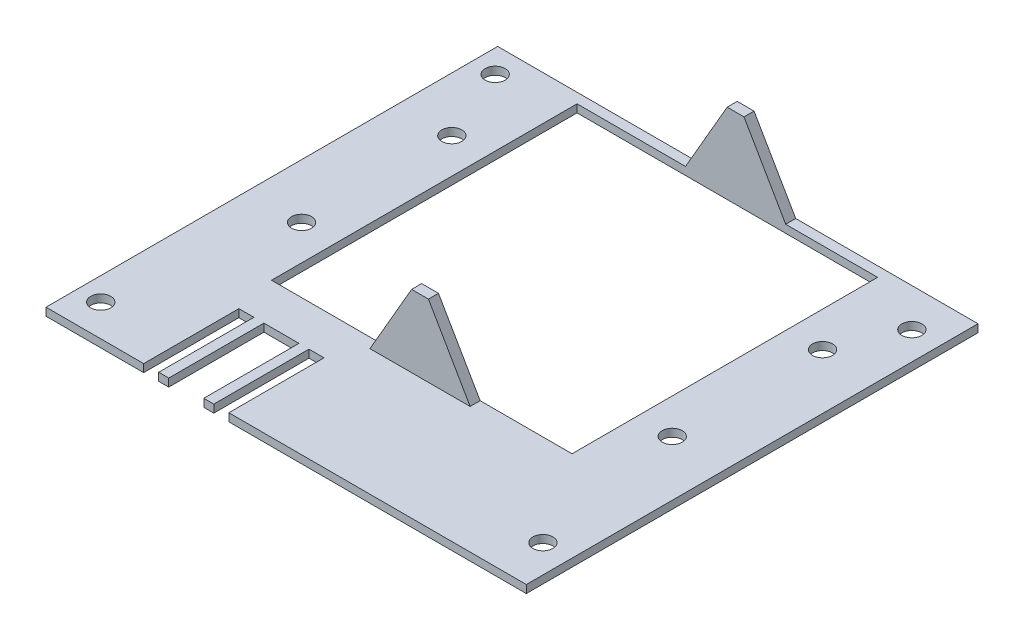
SolidWorks part; units mm, degrees
material "ABS"
ref_plane "Front Plane" through (0, 0, 0) normal (0, 0, 1) x (1, 0, 0)
ref_plane "Top Plane" through (0, 0, 0) normal (0, 1, 0) x (1, 0, 0)
ref_plane "Right Plane" through (0, 0, 0) normal (1, 0, 0) x (0, 0, -1)
sketch "Sketch1" plane through (0, 0, 0) normal (0, 1, 0) x (1, 0, 0)
  line L1 (-32.2441, 108.719) -> (64.6459, 108.719)
  line L2 (-32.2441, 108.719) -> (-32.2441, 18.549)
  line L3 (-32.2441, 18.549) -> (64.6459, 18.549)
  line L4 (64.6459, 108.719) -> (64.6459, 18.549)
  dimension "D1" = 96.89
  dimension "D2" = 90.17
extrude "PCB" add sketch "Sketch1" along normal blind 1.57
sketch "Sketch2" plane through (0, 1.57, 0) normal (0, 1, 0) x (1, 0, 0)
  line L1 (-32.2441, 18.549) -> (64.6459, 18.549) construction
  line L2 (-32.2441, 108.719) -> (-32.2441, 18.549) construction
  line L3 (-32.2441, 18.549) -> (64.6459, 18.549) construction
  circle A0 centre (58.5659, 27.439) radius 2
  circle A1 centre (-27.1641, 24.899) radius 2
  circle A2 centre (-27.1641, 103.639) radius 2
  circle A3 centre (58.5659, 101.099) radius 2
  dimension "D3" = 4
  dimension "D6" = 4
  dimension "D11" = 4
  dimension "D12" = 4
  dimension "D2" = 90.81
  dimension "D4" = 90.81
  dimension "D5" = 6.35
  dimension "D7" = 5.08
  dimension "D8" = 5.08
  dimension "D9" = 82.55
  dimension "D10" = 85.09
  dimension "D13" = 8.89
extrude "M3 Mounting Holes" cut sketch "Sketch2" against normal blind 1.57
sketch "Sketch3" plane through (0, 1.57, 0) normal (0, 1, 0) x (1, 0, 0)
  line L0 (64.6459, 108.719) -> (-32.2441, 108.719) construction
  line L1 (12.7559, 108.719) -> (22.7559, 108.719)
  line L2 (12.7559, 108.719) -> (12.7559, 106.719)
  line L3 (12.7559, 106.719) -> (22.7559, 106.719)
  line L4 (22.7559, 108.719) -> (22.7559, 106.719)
  line L5 (-32.2441, 108.719) -> (-32.2441, 18.549) construction
  line L7 (12.7559, 45.719) -> (22.7559, 45.719)
  line L8 (12.7559, 45.719) -> (12.7559, 43.719)
  line L9 (12.7559, 43.719) -> (22.7559, 43.719)
  line L10 (22.7559, 45.719) -> (22.7559, 43.719)
  dimension "D1" = 2
  dimension "D2" = 10
  dimension "D3" = 0
  dimension "D4" = 45
  dimension "D5" = 61
  dimension "D6" = 2
  dimension "D7" = 45
extrude "Boss-Extrude1" [suppressed] add sketch "Sketch3" along normal blind 10
sketch "Sketch4" plane through (0, 1.57, 0) normal (0, 1, 0) x (1, 0, 0)
  line L0 (64.6459, 108.719) -> (-32.2441, 108.719) construction
  line L1 (64.6459, 108.719) -> (-32.2441, 108.719) construction
  line L2 (-32.2441, 108.719) -> (-32.2441, 18.549) construction
  line L3 (64.6459, 108.719) -> (-32.2441, 108.719) construction
  circle A0 centre (-20.8941, 88.719) radius 2
  circle A1 centre (53.1059, 88.719) radius 2
  circle A2 centre (-20.8941, 58.719) radius 2
  circle A3 centre (53.1059, 58.719) radius 2
  dimension "D1" = 4
  dimension "D2" = 4
  dimension "D7" = 4
  dimension "D8" = 4
  dimension "D12" = 74
  dimension "D3" = 20
  dimension "D4" = 20
  dimension "D5" = 74
  dimension "D6" = 11.35
  dimension "D9" = 50
  dimension "D10" = 50
  dimension "D11" = 11.35
extrude "Cut-Extrude1" cut sketch "Sketch4" against normal blind 23
ref_plane "Plane1" through (0, 0, -45.719) normal (0, 0, 1) x (1, 0, 0)
sketch "Sketch7" plane through (0, 0, -45.719) normal (0, 0, 1) x (1, 0, 0)
  line L0 (27.7559, 1.57) -> (19.4384, 15.9764)
  line L1 (19.4384, 15.9764) -> (16.0735, 15.9764)
  line L2 (16.0735, 15.9764) -> (7.7559, 1.57)
  line L3 (7.7559, 1.57) -> (27.7559, 1.57)
  line L4 (-32.2441, 1.57) -> (64.6459, 1.57) construction
  dimension "D1" = 60
  dimension "D2" = 60
  dimension "D3" = 0
  dimension "D4" = 3.3649
  dimension "D5" = 20
  dimension "D6" = 5
ref_plane "Plane2" through (0, 0, -108.719) normal (0, 0, 1) x (1, 0, 0)
sketch "Sketch8" plane through (0, 0, -108.719) normal (0, 0, 1) x (1, 0, 0)
  line L0 (27.7559, 1.57) -> (19.4384, 15.9764) construction
  line L1 (19.4384, 15.9764) -> (16.0735, 15.9764) construction
  line L2 (16.0735, 15.9764) -> (7.7559, 1.57) construction
  line L3 (7.7559, 1.57) -> (27.7559, 1.57) construction
  line L4 (27.7559, 1.57) -> (19.4384, 15.9764)
  line L5 (19.4384, 15.9764) -> (16.0735, 15.9764)
  line L6 (16.0735, 15.9764) -> (7.7559, 1.57)
  line L7 (7.7559, 1.57) -> (27.7559, 1.57)
extrude "Boss-Extrude2" add sketch "Sketch7" along normal blind 2
extrude "Boss-Extrude3" add sketch "Sketch8" along normal blind 2
sketch "Sketch9" plane through (0, 1.57, 0) normal (0, 1, 0) x (1, 0, 0)
  line L0 (-32.2441, 18.549) -> (64.6459, 18.549) construction
  line L1 (-9.2441, 18.549) -> (-12.2441, 18.549)
  line L2 (-9.2441, 18.549) -> (-9.2441, 37.549)
  line L3 (-9.2441, 37.549) -> (-12.2441, 37.549)
  line L4 (-12.2441, 18.549) -> (-12.2441, 37.549)
  line L5 (-32.2441, 108.719) -> (-32.2441, 18.549) construction
  line L6 (-7.2441, 18.549) -> (-0.2441, 18.549)
  line L7 (-7.2441, 18.549) -> (-7.2441, 37.549)
  line L8 (-7.2441, 37.549) -> (-0.2441, 37.549)
  line L9 (-0.2441, 18.549) -> (-0.2441, 37.549)
  line L11 (1.7559, 18.549) -> (4.7559, 18.549)
  line L12 (1.7559, 18.549) -> (1.7559, 37.549)
  line L13 (1.7559, 37.549) -> (4.7559, 37.549)
  line L14 (4.7559, 18.549) -> (4.7559, 37.549)
  dimension "D1" = 19
  dimension "D2" = 19
  dimension "D3" = 2
  dimension "D4" = 3
  dimension "D5" = 7
  dimension "D6" = 20
  dimension "D7" = 3
  dimension "D8" = 19
  dimension "D9" = 2
extrude "Cut-Extrude2" cut sketch "Sketch9" against normal through all
sketch "Sketch10" plane through (0, 1.57, 0) normal (0, 1, 0) x (1, 0, 0)
  line L0 (7.7559, 108.719) -> (-32.2441, 108.719) construction
  line L1 (-32.2441, 18.549) -> (-31.7441, 18.549)
  line L2 (-32.2441, 18.549) -> (-32.2441, 108.719)
  line L3 (-32.2441, 108.719) -> (-31.7441, 108.719)
  line L4 (-31.7441, 18.549) -> (-31.7441, 108.719)
  line L5 (64.6459, 108.719) -> (27.7559, 108.719) construction
  line L6 (64.6459, 18.549) -> (64.1459, 18.549)
  line L7 (64.6459, 18.549) -> (64.6459, 108.719)
  line L8 (64.6459, 108.719) -> (64.1459, 108.719)
  line L9 (64.1459, 18.549) -> (64.1459, 108.719)
  dimension "D1" = 0.5
  dimension "D2" = 0.5
extrude "Cut-Extrude3" cut sketch "Sketch10" against normal blind 10
sketch "Sketch11" plane through (0, 1.57, 0) normal (0, 1, 0) x (1, 0, 0)
  line L0 (7.7559, 106.719) -> (27.7559, 106.719) construction
  line L1 (-13.8941, 106.719) -> (46.1059, 106.719)
  line L2 (-13.8941, 106.719) -> (-13.8941, 45.719)
  line L3 (-13.8941, 45.719) -> (46.1059, 45.719)
  line L4 (46.1059, 106.719) -> (46.1059, 45.719)
  dimension "D1" = 60
  dimension "D2" = 61
  dimension "D3" = 0
  dimension "D4" = 7
extrude "Cut-Extrude4" cut sketch "Sketch11" against normal blind 10
